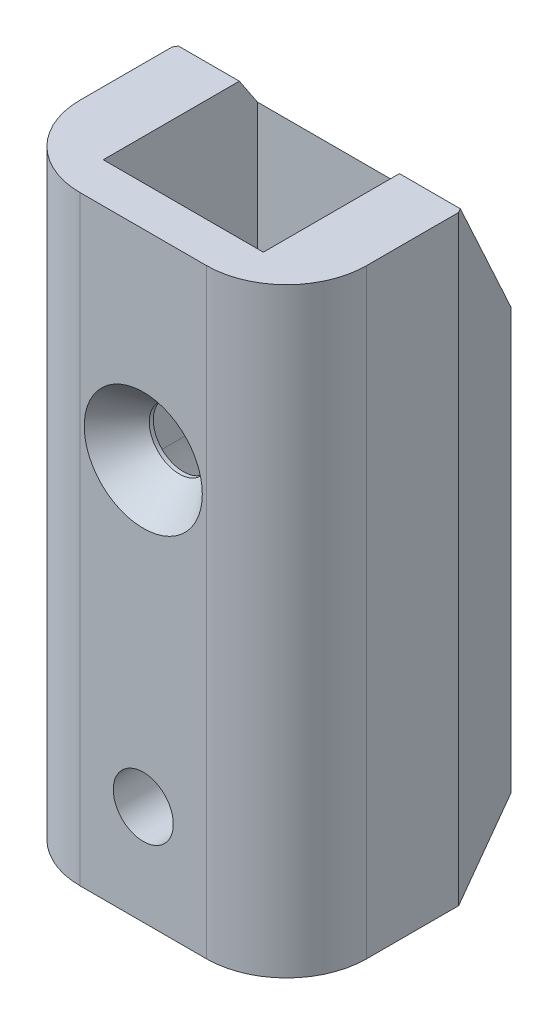
SolidWorks part; units mm, degrees
ref_plane "Alzado" through (0, 0, 0) normal (0, 0, 1) x (1, 0, 0)
ref_plane "Planta" through (0, 0, 0) normal (0, 1, 0) x (1, 0, 0)
ref_plane "Vista lateral" through (0, 0, 0) normal (1, 0, 0) x (0, 0, -1)
sketch "Croquis1" plane through (0, 0, 0) normal (0, 1, 0) x (1, 0, 0)
  line L1 (7.1591, 0) -> (3.5796, 6.2)
  line L2 (3.5796, 6.2) -> (-3.5796, 6.2)
  line L3 (-3.5796, 6.2) -> (-7.1591, 0)
  line L4 (-7.1591, 0) -> (-3.5796, -6.2)
  line L5 (-3.5796, -6.2) -> (3.5796, -6.2)
  line L6 (3.5796, -6.2) -> (7.1591, 0)
  circle A0 centre (0, 0) radius 5
  circle A1 centre (0, 0) radius 6.2 construction
  dimension "D1" = 10
  dimension "D2" = 12.4
extrude "Saliente-Extruir1" add sketch "Croquis1" against normal blind 10
sketch "Croquis3" plane through (0, 0, 0) normal (0, 0, 1) x (1, 0, 0)
  line L0 (0, 0) -> (0, 2) construction
  line L1 (0, 2) -> (0, 6) construction
  line L2 (0, 6) -> (0, 20) construction
  line L3 (-4, 6) -> (4, 6) construction
  line L4 (-4, 20) -> (4, 20)
  line L5 (-4, 6) -> (-4, 20)
  line L6 (4, 6) -> (4, 20)
  line L7 (-7.1591, 0) -> (-7.1591, 20)
  line L8 (-7.1591, 20) -> (-4, 20)
  line L9 (7.1591, 0) -> (7.1591, 20)
  line L10 (7.1591, 20) -> (4, 20)
  line L11 (0, 6) -> (0, 10) construction
  line L12 (-3.2, 6) -> (-3.2, 10)
  line L13 (3.2, 6) -> (3.2, 10)
  line L14 (-7.1591, 0) -> (7.1591, 0)
  arc A3 (-4, 6) -> (4, 6) centre (0, 6) ccw
  circle A4 centre (0, 6) radius 1.5
  circle A5 centre (0, 10) radius 1.5
  arc A6 (-3.2, 6) -> (3.2, 6) centre (0, 6) ccw
  arc A7 (3.2, 10) -> (-3.2, 10) centre (0, 10) ccw
  point P12 (0, 6)
  point P15 (0, 20)
  point P21 (0, 8)
  dimension "D2" = 4
  dimension "D4" = 3
  dimension "D5" = 4
  dimension "D1" = 2
  dimension "D3" = 14
  dimension "D6" = 6.4
extrude "Saliente-Extruir2" add sketch "Croquis3" along normal blind 2 from offset 6.6 separate body contours L5 A3 L6 L4 A7 L13 A6 L12 | L13 A7 L12 A6 A4 A5 | A4 region at (0, 13.8852, 0) region at (0, 8, 0) region at (0, 6, 0)
extrude "Saliente-Extruir3" add sketch "Croquis3<3>" against normal up to surface (6.2 mm away) from offset 3.3 separate body contours L13 A7 L12 A6 A4 A5 | A5 region at (0, 8, 0) region at (0, 10, 0) up to face at (0, -5, -6.2) offset against normal yes
sketch "Croquis3<3>" plane through (0, 0, 0) normal (0, 0, 1) x (1, 0, 0) same geometry as "Croquis3"
extrude "Saliente-Extruir4" add sketch "Croquis3<4>" against normal up to surface (6.2 mm away) from offset 1.1 contours L5 A3 L6 L4 A7 L13 A6 L12 region at (0, 13.8852, 0) up to face at (0, -5, -6.2) offset against normal yes
sketch "Croquis3<4>" plane through (0, 0, 0) normal (0, 0, 1) x (1, 0, 0) same geometry as "Croquis3"
extrude "Saliente-Extruir5" add sketch "Croquis3<6>" along normal up to surface (8.6 mm away) and the other way up to surface (6.2 mm away) contours A3 L5 L8 L7 L14 L9 L10 L6 region at (-4.246, 13, 0) up to face at (0, 12, 8.6) other way up to face at (-1.5, 6, -6.2)
sketch "Croquis3<6>" plane through (0, 0, 0) normal (0, 0, 1) x (1, 0, 0) same geometry as "Croquis3"
ref_plane "Plano1" through (0, -10, 0) normal (0, -1, 0) x (-1, 0, 0)
sketch "Croquis4" plane through (0, -10, 0) normal (0, -1, 0) x (-1, 0, 0)
  line L0 (3.5796, 6.2) -> (7.1591, 0) construction
  line L1 (7.1591, 0) -> (3.5796, 6.2)
  line L2 (3.5796, 6.2) -> (-3.5796, 6.2)
  line L3 (-3.5796, 6.2) -> (-7.1591, 0)
  line L4 (-7.1591, 0) -> (-3.5796, -6.2)
  line L5 (-3.5796, -6.2) -> (3.5796, -6.2)
  line L6 (3.5796, -6.2) -> (7.1591, 0)
  line L7 (7.1591, 0) -> (3.5796, -6.2) construction
  line L8 (-7.1591, 0) -> (-7.1591, 6.2)
  line L9 (-7.1591, 6.2) -> (-3.5796, 6.2)
  line L10 (3.5796, 6.2) -> (7.1591, 6.2)
  line L11 (7.1591, 6.2) -> (7.1591, 0)
  line L12 (-7.1591, 0) -> (-7.1591, -8.6)
  line L13 (7.1591, -8.6) -> (-7.1591, -8.6) construction
  line L14 (-7.1591, -8.6) -> (-7.1591, 0) construction
  line L15 (-7.1591, -8.6) -> (7.1591, -8.6)
  line L16 (7.1591, -8.6) -> (7.1591, 0)
  circle A0 centre (0, 0) radius 6.2 construction
extrude "Cortar-Extruir1" cut sketch "Croquis4" along direction (0, -1, 0) on the side against the normal through all contours L11 L10 L1 | L9 L8 L3 region at (-5.966, -10, -4.1333) region at (5.966, -10, -4.1333)
extrude "Saliente-Extruir6" add sketch "Croquis4<3>" against normal up to surface (10 mm away) contours L15 L16 L6 L5 L4 L12 region at (-6.9921, -10, 4.3) up to face at (0, 0, 4.9333)
sketch "Croquis4<3>" plane through (0, -10, 0) normal (0, -1, 0) x (-1, 0, 0) same geometry as "Croquis4"
ref_plane "Plano2" through (0, 0, -6.2) normal (0, 0, -1) x (-1, 0, 0)
sketch "Croquis5" plane through (0, 0, -6.2) normal (0, 0, -1) x (-1, 0, 0)
  line L0 (0, -10) -> (0, -5) construction
  line L1 (-7.8751, -10) -> (7.8751, -10) construction
  circle A0 centre (0, -5) radius 1.5
  dimension "D1" = 3
  dimension "D2" = 5
extrude "Cortar-Extruir2" cut sketch "Croquis5" against normal through all
chamfer "Chaflán1" distance 1.45 distance2 1.8 1 edges at (1.5, 10, 8.6) first distance on face at (-1.5, -5, 8.6)
chamfer "Chaflán2" distance 1.45 distance2 1.8 1 edges at (-1.5, 6, -6.2) first distance on face at (1.5, 6, -3.3)
fillet "Redondeo1" radius 4 2 edges at (7.1591, 5, 8.6) (-7.1591, 5, 8.6)
sketch "Croquis6" plane through (0, 0, 0) normal (1, 0, 0) x (0, 0, -1)
  line L5 (6.2, 20) -> (0.2, 20)
  line L6 (6.2, 20) -> (0, 20) construction
  line L7 (0.2, 20) -> (6.2, 11)
  line L8 (6.2, -10) -> (6.2, 20) construction
  line L9 (6.2, 11) -> (6.2, 20)
  dimension "D1" = 9
  dimension "D2" = 6
extrude "Cortar-Extruir3" cut sketch "Croquis6" along normal through all and the other way through all
